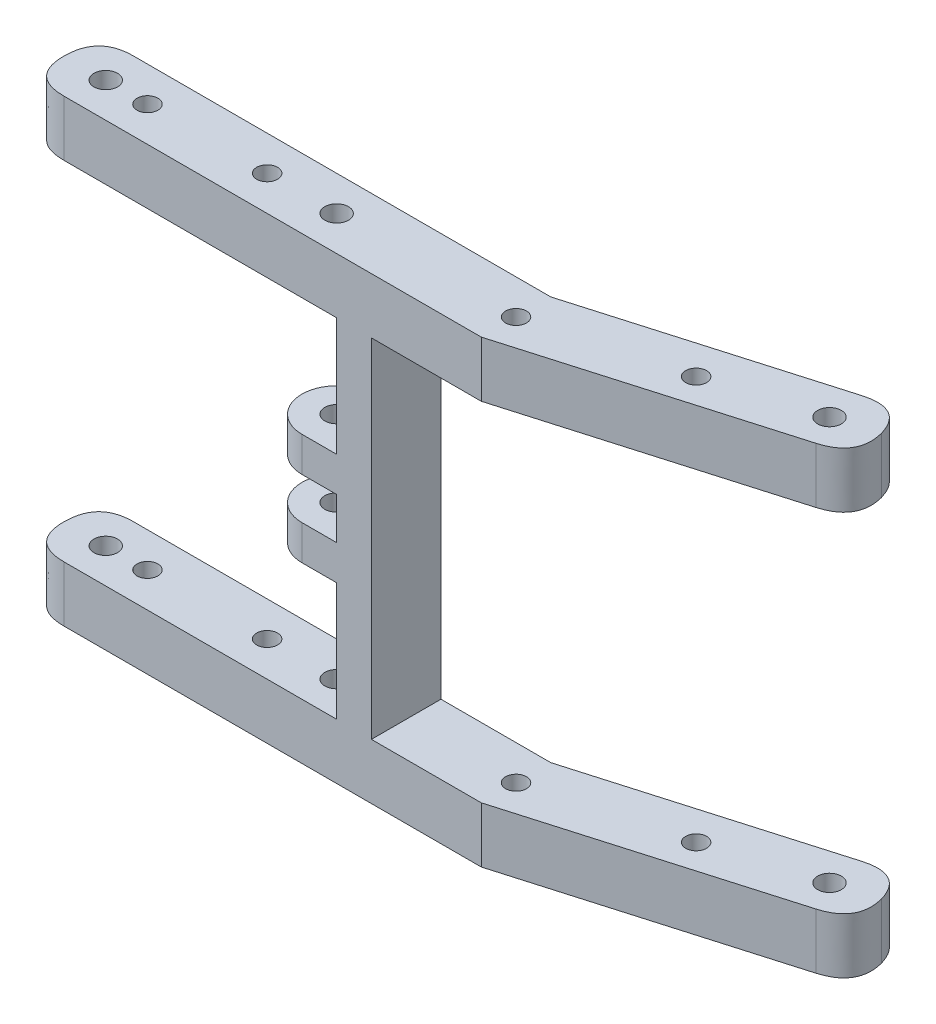
SolidWorks part; units mm, degrees
ref_plane "Front Plane" through (0, 0, 0) normal (0, 0, 1) x (1, 0, 0)
ref_plane "Top Plane" through (0, 0, 0) normal (0, 1, 0) x (1, 0, 0)
ref_plane "Right Plane" through (0, 0, 0) normal (1, 0, 0) x (0, 0, -1)
sketch "Sketch1" plane through (0, 0, 0) normal (0, 1, 0) x (1, 0, 0)
  line L3 (0, -4.2034) -> (0, 5.7966) construction
  line L5 (0, 5.7966) -> (-65, 5.7966)
  line L6 (0, -4.2034) -> (-65, -4.2034)
  line L7 (-65, -4.2034) -> (-65, 5.7966)
  line L8 (0, 5.7966) -> (39.5, 17.2764)
  line L9 (0, -4.2034) -> (42, 8.003)
  line L10 (42, 8.003) -> (39.5, 17.2764)
  dimension "D1" = 10
  dimension "D2" = 39.5
  dimension "D3" = 42
  dimension "D4" = 65
extrude "Boss-Extrude1" add sketch "Sketch1" along normal blind 8
sketch "Sketch2" plane through (0, 8, 0) normal (0, 1, 0) x (1, 0, 0)
  line L0 (-65, 0.7966) -> (-6.7929, 0.7966) construction
  line L1 (-65, 5.7966) -> (-65, -4.2034) construction
  line L2 (0, 5.7966) -> (0, -4.2034) construction
  line L3 (42, 8.003) -> (39.5, 17.2764) construction
  line L4 (40.75, 12.6397) -> (0, 0) construction
  circle A0 centre (-59, 0.7966) radius 1.7
  circle A1 centre (-53, 0.7966) radius 1.5
  circle A2 centre (-35.7929, 0.7966) radius 1.5
  circle A8 centre (20.375, 6.3198) radius 1.5
  circle A9 centre (35.0153, 10.8609) radius 1.7
  circle A10 centre (0, 0.7966) radius 1.5
  dimension "D1" = 3
  dimension "D2" = 3.4
  dimension "D3" = 3
  dimension "D6" = 3
  dimension "D7" = 3
  dimension "D8" = 3.4
  dimension "D15" = 6
  dimension "D16" = 6
  dimension "D9" = 6
extrude "Cut-Extrude1" cut sketch "Sketch2" against normal blind 10
fillet "Fillet1" radius 5 2 edges at (-65, 4, 4.2034) (-65, 4, -5.7966) conic rho 0.5
fillet "Fillet2" radius 5 2 edges at (39.5, 4, -17.2764) (42, 4, -8.003) conic rho 0.5
sketch "Sketch3" plane through (0, 8, 0) normal (0, 1, 0) x (1, 0, 0)
  circle A0 centre (-25.7929, 0.7966) radius 5
  circle A1 centre (-35.7929, 0.7966) radius 1.5 construction
  dimension "D1" = 10
  dimension "D3" = 10
extrude "Boss-Extrude2" add sketch "Sketch3" along normal blind 22
sketch "Sketch4" plane through (0, 30, 0) normal (0, 1, 0) x (1, 0, 0)
  circle A0 centre (-25.7929, 0.7966) radius 1.7
  dimension "D1" = 3.4
extrude "Cut-Extrude2" cut sketch "Sketch4" against normal through all
sketch "Sketch6" plane through (0, 8, 0) normal (0, 1, 0) x (1, 0, 0)
  line L1 (-15.7929, 5.7966) -> (-25.7929, 5.7966)
  line L2 (-15.7929, 5.7966) -> (-15.7929, -4.2034)
  line L3 (-15.7929, -4.2034) -> (-25.7929, -4.2034)
  line L5 (-15.7929, 5.7966) -> (-25.7929, -4.2034) construction
  line L6 (-15.7929, -4.2034) -> (-25.7929, 5.7966) construction
  arc A0 (-25.7929, -4.2034) -> (-25.7929, 5.7966) centre (-25.7929, 0.7966) ccw construction
  arc A1 (-25.7929, -4.2034) -> (-25.7929, 5.7966) centre (-25.7929, 0.7966) ccw
  point P0 (-20.7929, 0.7966)
extrude "Boss-Extrude4" add sketch "Sketch6" along normal blind 22
ref_plane "Plane2" through (0, 25, 0) normal (0, 1, 0) x (1, 0, 0)
sketch "Sketch9" plane through (0, 25, 0) normal (0, 1, 0) x (1, 0, 0)
  line L6 (-25.7929, 5.7966) -> (-20.7929, 5.7966)
  line L8 (-25.7929, -4.2034) -> (-20.7929, -4.2034)
  line L9 (-20.7929, 5.7966) -> (-20.7929, -4.2034)
  arc A1 (-25.7929, 5.7966) -> (-25.7929, -4.2034) centre (-25.7929, 0.7966) ccw
  circle A2 centre (-25.7929, 0.7966) radius 1.7
  dimension "D1" = 3.4
extrude "Cut-Extrude3" cut sketch "Sketch9" against normal blind 17
sketch "Sketch10" plane through (0, 30, 0) normal (0, 1, 0) x (1, 0, 0)
  line L0 (-15.7929, 5.7966) -> (-25.7929, 5.7966) construction
  line L1 (-15.7929, -4.2034) -> (-20.7929, -4.2034)
  line L2 (-15.7929, -4.2034) -> (-15.7929, 5.7966)
  line L3 (-15.7929, 5.7966) -> (-20.7929, 5.7966)
  line L4 (-20.7929, -4.2034) -> (-20.7929, 5.7966)
extrude "Boss-Extrude5" add sketch "Sketch10" along normal blind 3
ref_plane "Plane3" through (0, 33, 0) normal (0, 1, 0) x (1, 0, 0)
mirror "Mirror1" about plane through (0, 33, 0) normal (0, 1, 0) of bodies 109
